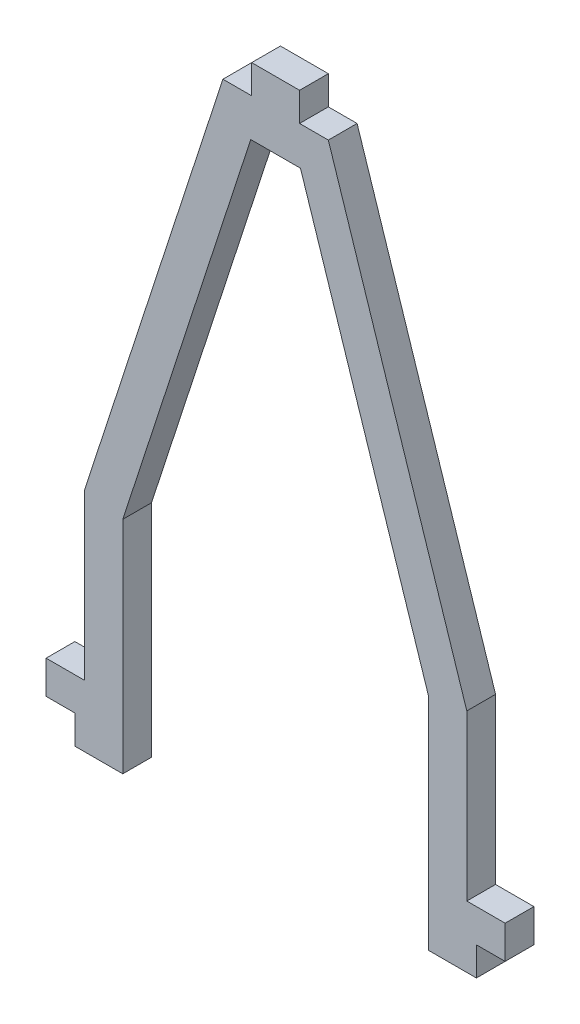
SolidWorks part; units mm, degrees
material "Custom Plastic"
ref_plane "Front Plane" through (0, 0, 0) normal (0, 0, 1) x (1, 0, 0)
ref_plane "Top Plane" through (0, 0, 0) normal (0, 1, 0) x (1, 0, 0)
ref_plane "Right Plane" through (0, 0, 0) normal (1, 0, 0) x (0, 0, -1)
sketch "Sketch1" plane through (0, 0, 0) normal (0, 0, 1) x (1, 0, 0)
  line L20 (-6.3839, -66.0934) -> (-6.3839, -43.0934)
  line L38 (-6.3839, -43.0934) -> (6.9701, -2.0934)
  line L39 (6.9701, -2.0934) -> (12.1621, -2.0934)
  line L40 (9.5661, -2.0934) -> (9.5661, 4.9066) construction
  line L41 (7.0661, 4.9066) -> (12.0661, 4.9066)
  line L42 (12.0661, 4.9066) -> (12.0661, 1.9066)
  line L44 (4.0661, 1.9066) -> (-10.3839, -42.4584)
  line L45 (-10.3839, -42.4584) -> (-10.3839, -59.6388)
  line L46 (-10.3839, -59.6388) -> (-14.3839, -59.6388)
  line L47 (-14.3839, -59.6388) -> (-14.3839, -63.0934)
  line L48 (-14.3839, -63.0934) -> (-11.3839, -63.0934)
  line L49 (-11.3839, -63.0934) -> (-11.3839, -66.0934)
  line L50 (-11.3839, -66.0934) -> (-6.3839, -66.0934)
  line L51 (-10.3839, -42.4584) -> (-6.3839, -43.0934) construction
  line L52 (4.0661, 1.9066) -> (6.9701, -2.0934) construction
  line L53 (15.0661, 1.9066) -> (12.1621, -2.0934) construction
  line L54 (29.5161, -42.4584) -> (25.5161, -43.0934) construction
  line L55 (30.5161, -66.0934) -> (25.5161, -66.0934)
  line L56 (30.5161, -63.0934) -> (30.5161, -66.0934)
  line L57 (33.5161, -63.0934) -> (30.5161, -63.0934)
  line L58 (33.5161, -59.6388) -> (33.5161, -63.0934)
  line L59 (29.5161, -59.6388) -> (33.5161, -59.6388)
  line L60 (29.5161, -42.4584) -> (29.5161, -59.6388)
  line L61 (15.0661, 1.9066) -> (29.5161, -42.4584)
  line L63 (7.0661, 4.9066) -> (7.0661, 1.9066)
  line L64 (25.5161, -43.0934) -> (12.1621, -2.0934)
  line L65 (25.5161, -66.0934) -> (25.5161, -43.0934)
  line L66 (4.0661, 1.9066) -> (7.0661, 1.9066)
  line L67 (12.0661, 1.9066) -> (15.0661, 1.9066)
  point P28 (7.0661, 3.4066)
  dimension "D1" = 3
  dimension "D2" = 3
  dimension "D3" = 4
  dimension "D4" = 5
  dimension "D5" = 4
  dimension "D6" = 65
  dimension "D7" = 41.9
  dimension "D8" = 20
  dimension "D9" = 4
  dimension "D10" = 5
  dimension "D11" = 3
  dimension "D12" = 3
extrude "Boss-Extrude1" add sketch "Sketch1" along normal blind 3
